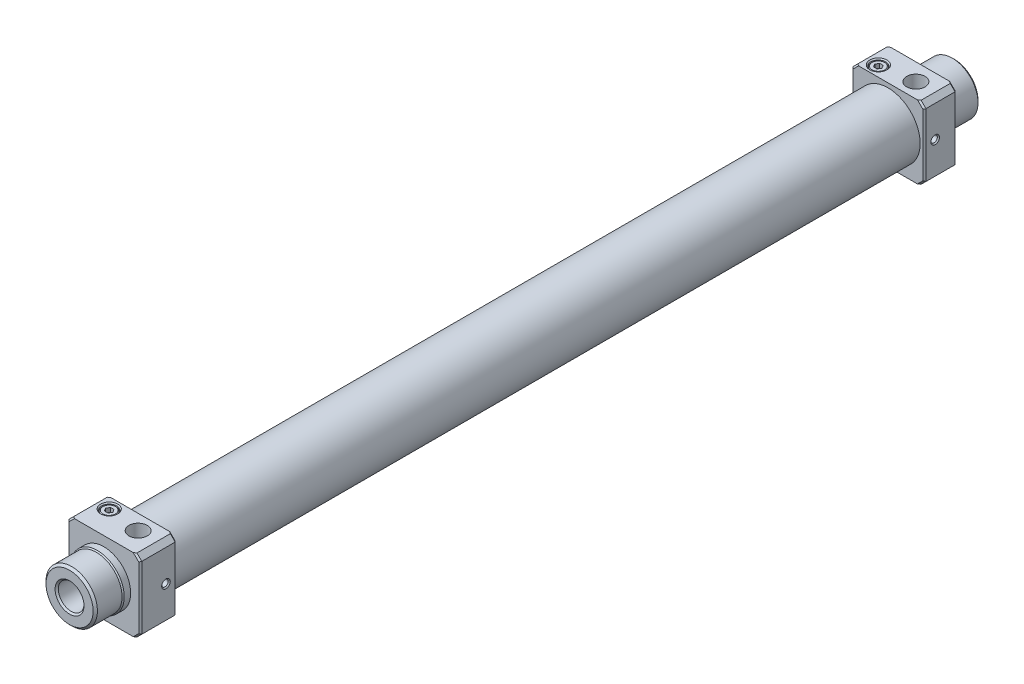
SolidWorks part; units mm, degrees
material "Low Carbon Steel"
ref_plane "Front" through (0, 0, 0) normal (0, 0, 1) x (1, 0, 0)
ref_plane "Top" through (0, 0, 0) normal (0, 1, 0) x (1, 0, 0)
ref_plane "Right" through (0, 0, 0) normal (1, 0, 0) x (0, 0, -1)
ref_plane "Plane1" through (0, 0, -1) normal (0, 0, 1) x (1, 0, 0)
sketch "Sketch1" plane through (0, 0, 0) normal (0, 0, 1) x (1, 0, 0)
  circle A0 centre (0, 0) radius 15
  dimension "D1" = 30
extrude "Boss-Extrude1" add sketch "Sketch1" along normal mid plane 381
sketch "Sketch2" plane through (0, 0, 190.5) normal (0, 0, 1) x (1, 0, 0)
  line L1 (-17, -17) -> (17, -17)
  line L2 (-17, -17) -> (-17, 17)
  line L3 (-17, 17) -> (17, 17)
  line L4 (17, -17) -> (17, 17)
  line L5 (-17, -17) -> (17, 17) construction
  line L6 (-17, 17) -> (17, -17) construction
  point P0 (0, 0)
  dimension "D1" = 34
extrude "Boss-Extrude2" add sketch "Sketch2" against normal blind 17
sketch "Sketch3" plane through (0, 0, -190.5) normal (0, 0, -1) x (-1, 0, 0)
  line L1 (-17, -17) -> (17, -17)
  line L2 (-17, -17) -> (-17, 17)
  line L3 (-17, 17) -> (17, 17)
  line L4 (17, -17) -> (17, 17)
  line L5 (-17, -17) -> (17, 17) construction
  line L6 (-17, 17) -> (17, -17) construction
  point P0 (0, 0)
extrude "Boss-Extrude3" add sketch "Sketch3" against normal blind 15
chamfer "Chamfer2" distance 2.26 angle 45 8 edges at (-17, -17, -183) (17, -17, -183) (-17, -17, 182) (17, -17, 182) (17, 17, -183) (-17, 17, -183) (-17, 17, 182) (17, 17, 182)
chamfer "Chamfer3" distance 0.707 angle 45 24 edges at (17, 0, -175.5) (17, 0, -190.5) (-17, 0, -190.5) (-17, 0, -175.5) (-17, 0, 173.5) (-17, 0, 190.5) (17, 0, 173.5) (17, 0, 190.5) (15.87, -15.87, -175.5) (15.87, 15.87, -175.5) (15.87, -15.87, -190.5) (15.87, 15.87, -190.5) (-15.87, 15.87, -190.5) (-15.87, -15.87, -190.5) (-15.87, 15.87, -175.5) (-15.87, -15.87, -175.5) (-15.87, -15.87, 173.5) (-15.87, 15.87, 173.5) (-15.87, -15.87, 190.5) (-15.87, 15.87, 190.5) (15.87, -15.87, 173.5) (15.87, 15.87, 173.5) (15.87, -15.87, 190.5) (15.87, 15.87, 190.5)
sketch "Sketch4" plane through (0, 0, -190.5) normal (0, 0, -1) x (-1, 0, 0)
  circle A0 centre (0, 0) radius 12.5
  dimension "D1" = 25
extrude "Boss-Extrude4" add sketch "Sketch4" along normal blind 3
sketch "Sketch5" plane through (0, 0, 190.5) normal (0, 0, 1) x (1, 0, 0)
  circle A0 centre (0, 0) radius 12.5
  dimension "D1" = 25
extrude "Boss-Extrude5" add sketch "Sketch5" along normal blind 3
sketch "Sketch8" plane through (0, 0, 193.5) normal (0, 0, 1) x (1, 0, 0)
  circle A0 centre (0, 0) radius 12
  dimension "D1" = 24
extrude "Boss-Extrude6" add sketch "Sketch8" along normal blind 13
chamfer "Chamfer4" distance 0.5 angle 45 1 edges at (12, 0, 193.5)
sketch "Sketch9" plane through (0, 0, -193.5) normal (0, 0, -1) x (-1, 0, 0)
  circle A0 centre (0, 0) radius 12
  dimension "D1" = 24
extrude "Boss-Extrude7" add sketch "Sketch9" along normal blind 13
chamfer "Chamfer5" distance 0.5 angle 45 1 edges at (-12, 0, -193.5)
chamfer "Chamfer6" distance 1 angle 45 1 edges at (12, 0, 206.5)
chamfer "Chamfer10" distance 1 angle 45 1 edges at (-12, 0, -206.5)
sketch "Sketch6" plane through (0, 0, 0) normal (0, 0, 1) x (1, 0, 0)
  circle A0 centre (0, 0) radius 12.5
  dimension "D1" = 25
extrude "Cut-Extrude1" cut sketch "Sketch6" along normal mid plane 305
sketch "Sketch7" plane through (0, 0, 0) normal (0, 0, 1) x (1, 0, 0)
  circle A0 centre (0, 0) radius 6
  dimension "D1" = 12
extrude "Cut-Extrude2" cut sketch "Sketch7" along normal through all
chamfer "Chamfer7" distance 0.75 angle 45 1 edges at (6, 0, 206.5)
sketch "Sketch10" plane through (0, 17, 0) normal (0, 1, 0) x (1, 0, 0)
  line L0 (-12.5, -190.5) -> (12.5, -190.5) construction
  circle A0 centre (-9.5, -178.5) radius 3.3
  circle A1 centre (-9.5, -178.5) radius 3.5
  dimension "D1" = 6.6
  dimension "D4" = 7
  dimension "D2" = 12
  dimension "D3" = 9.5
extrude "Cut-Extrude3" cut sketch "Sketch10" against normal blind 2.5
sketch "Sketch12" plane through (0, 17, 0) normal (0, 1, 0) x (1, 0, 0)
  circle A0 centre (-9.5, -178.5) radius 3.3 construction
  circle A1 centre (-9.5, -178.5) radius 3.3
extrude "Cut-Extrude4" cut sketch "Sketch12" against normal blind 0.5
chamfer "Chamfer8" distance 0.35 angle 45 1 edges at (-9.5, 16.5, 181.8)
sketch "Sketch13" plane through (0, 16.5, 0) normal (0, 1, 0) x (1, 0, 0)
  line L1 (-7.8257, -178.5) -> (-8.6628, -177.05)
  line L2 (-8.6628, -177.05) -> (-10.3372, -177.05)
  line L3 (-10.3372, -177.05) -> (-11.1743, -178.5)
  line L4 (-11.1743, -178.5) -> (-10.3372, -179.95)
  line L5 (-10.3372, -179.95) -> (-8.6628, -179.95)
  line L6 (-8.6628, -179.95) -> (-7.8257, -178.5)
  circle A0 centre (-9.5, -178.5) radius 1.45 construction
  dimension "D1" = 2.9
extrude "Cut-Extrude5" cut sketch "Sketch13" against normal blind 2
sketch "Sketch14" plane through (0, 17, 0) normal (0, 1, 0) x (1, 0, 0)
  circle A0 centre (-9.5, -178.5) radius 4
  circle A1 centre (-9.5, -178.5) radius 3.5 construction
  circle A2 centre (-9.5, -178.5) radius 3.5
  dimension "D1" = 8
extrude "Cut-Extrude6" cut sketch "Sketch14" against normal blind 0.5
chamfer "Chamfer9" distance 0.5 angle 45 1 edges at (-9.5, 16.5, 182.5)
mirror "Mirror1" about plane through (0, 0, -1) normal (0, 0, 1) of "Chamfer9", "Cut-Extrude6", "Cut-Extrude5", "Chamfer8", "Cut-Extrude4", "Cut-Extrude3"
sketch "Sketch15" plane through (0, 0, -190.5) normal (0, 0, -1) x (-1, 0, 0)
  circle A0 centre (0, 0) radius 13.5
  dimension "D1" = 27
extrude "Boss-Extrude8" [suppressed] add sketch "Sketch15" along normal blind 0.5
sketch "Sketch16" [suppressed] plane through (0, 0, -191) normal (0, 0, -1) x (-1, 0, 0)
  line L0 (-8, 10.8743) -> (-8, -10.8743)
  line L1 (8, 10.8743) -> (8, -10.8743)
  line L2 (-8, 0) -> (8, 0) construction
  circle A0 centre (0, 0) radius 13.5 construction
  circle A1 centre (0, 0) radius 13.5 construction
  arc A2 (-8, -10.8743) -> (8, -10.8743) centre (0, 0) ccw
  arc A3 (8, 10.8743) -> (-8, 10.8743) centre (0, 0) ccw
  dimension "D1" = 16
extrude "Boss-Extrude9" [suppressed] add sketch "Sketch16" along normal blind 14
sketch "Sketch17" [suppressed] plane through (0, 0, -205) normal (0, 0, -1) x (-1, 0, 0)
  line L0 (-8, 10.8743) -> (-8, 0)
  line L1 (-8, 10.8743) -> (-8, 9.6047) construction
  line L2 (-8, 0) -> (8, 0)
  line L3 (8, -10.8743) -> (8, -8.9443) construction
  line L4 (8, 0) -> (8, 10.8743)
  arc A0 (8, 10.8743) -> (-8, 10.8743) centre (0, 0) ccw construction
  arc A1 (8, 10.8743) -> (-8, 10.8743) centre (0, 0) ccw
revolve "Revolve1" [suppressed] add sketch "Sketch17" angle 180 about L2
sketch "Sketch18" [suppressed] plane through (0, 0, 0) normal (1, 0, 0) x (0, 0, -1)
  line L0 (205, 10.8743) -> (205, 13.5) construction
  circle A0 centre (205, 0) radius 5
  dimension "D1" = 10
extrude "Cut-Extrude7" [suppressed] cut sketch "Sketch18" against normal through all and the other way through all
fillet "Fillet1" [suppressed] radius 0.5
sketch "Sketch19" plane through (17, 0, 0) normal (1, 0, 0) x (0, 0, -1)
  line L0 (-190.5, -14.4472) -> (-190.5, 14.4472) construction
  circle A0 centre (-178.5, 0) radius 1.5
  dimension "D1" = 3
  dimension "D2" = 12
extrude "Cut-Extrude8" cut sketch "Sketch19" against normal blind 6
mirror "Mirror3" about plane through (0, 0, -1) normal (0, 0, 1) of "Cut-Extrude8"
chamfer "Chamfer11" distance 0.5 angle 45 2 edges at (17, 0, 177) (17, 0, -179)
hole_wizard "G1/8 Tapped Hole1" positions "Sketch21" profile "Sketch20" tap size "G1/8" standard "Peddi DIN"
sketch "Sketch21" plane through (0, 17, 0) normal (0, 1, 0) x (-1, 0, 0)
  circle A0 centre (9.5, 178.5) radius 4 construction
  circle A1 centre (9.5, -180.5) radius 4 construction
  point P0 (-6, 180.5)
  point P2 (-6, -182.5)
  dimension "D1" = 2
  dimension "D3" = 2
  dimension "D2" = 15.5
  dimension "D4" = 15.5
sketch "Sketch20" plane through (6, 17, 180.5) normal (1, 0, 0) x (0, 0, 1)
  line L0 (0, 0) -> (0, 27.5735)
  line L1 (0, 27.5735) -> (4.283, 25)
  line L2 (4.283, 25) -> (4.283, 0)
  line L5 (4.283, 0) -> (0, 0)
  line L10 (0, 27.5735) -> (-4.283, 25) construction
  line L11 (0, -6.35) -> (0, 107.95) construction
  dimension "Tap Drill Dia." = 8.566
  dimension "Tap Drill Depth" = 25
  dimension "Drill Angle" = 118
cosmetic thread "Hole Thread1" parameters "D1"=20, "D2"=13.157
cosmetic thread "Hole Thread2" parameters "D1"=20, "D2"=13.157
other "Freeze***"
